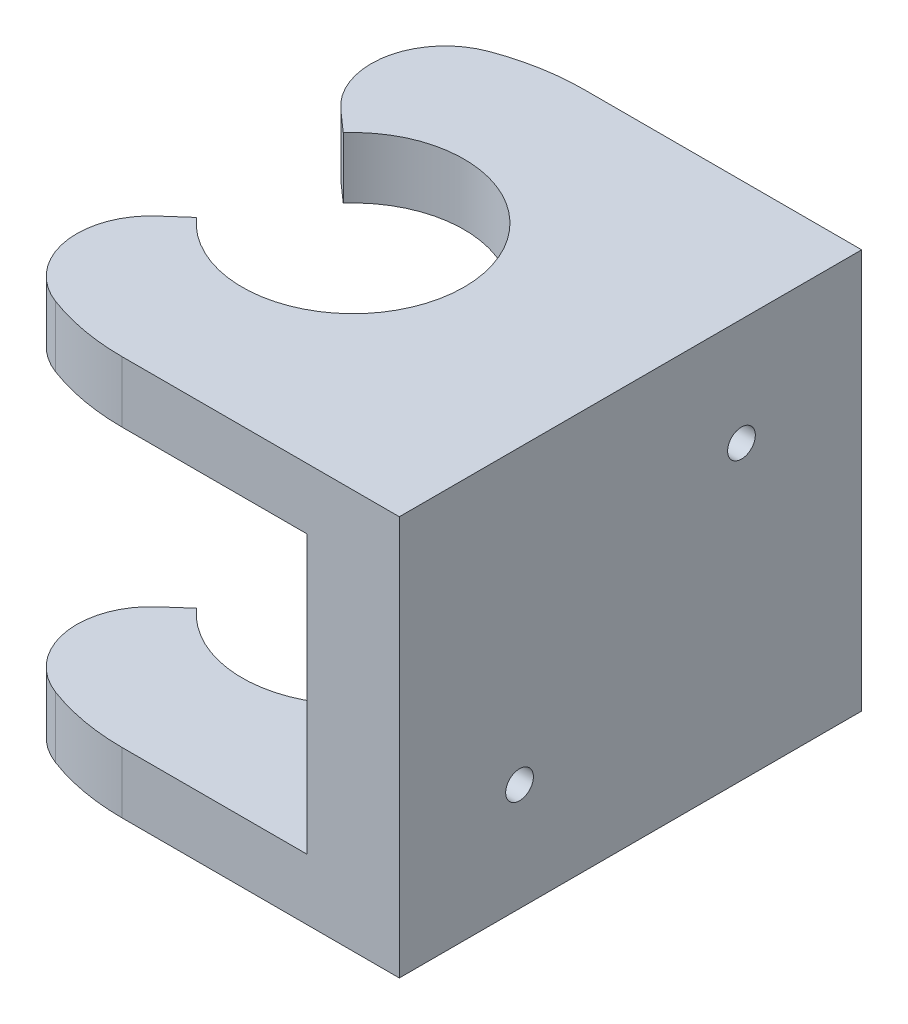
SolidWorks part; units mm, degrees
ref_plane "Front Plane" through (0, 0, 0) normal (0, 0, 1) x (1, 0, 0)
ref_plane "Top Plane" through (0, 0, 0) normal (0, 1, 0) x (1, 0, 0)
ref_plane "Right Plane" through (0, 0, 0) normal (1, 0, 0) x (0, 0, -1)
sketch "Sketch2" plane through (0, 0, 0) normal (0, 1, 0) x (1, 0, 0)
  line L0 (0, 0) -> (15, 0) construction
  line L1 (15, -12.5) -> (0, -12.5) construction
  line L2 (15, -12.5) -> (15, 12.5)
  line L3 (15, 12.5) -> (0, 12.5) construction
  line L5 (-9.375, 8.268) -> (-4.5, 3.9686)
  line L6 (-9.375, -8.268) -> (-4.5, -3.9686)
  line L8 (-4.5, 3.9686) -> (-4.5, -3.9686) construction
  line L9 (-4.5, 0) -> (0, 0) construction
  line L10 (0, 12.5) -> (15, 12.5)
  line L11 (15, -12.5) -> (0, -12.5)
  arc A0 (-4.5, -3.9686) -> (-4.5, 3.9686) centre (0, 0) ccw
  arc A1 (-9.375, -8.268) -> (0, -12.5) centre (0, 0) ccw
  arc A2 (0, 12.5) -> (-9.375, 8.268) centre (0, 0) ccw
  arc A3 (-9.375, -8.268) -> (-9.375, 8.268) centre (0, 0) ccw construction
  point P6 (-0.2805, 12.4969)
  point P7 (-0.2805, -12.5)
  point P16 (-11.8038, 12.5)
  dimension "D1" = 4.5
  dimension "D6" = 6.5
  dimension "D2" = 25
  dimension "D3" = 15
  dimension "D4" = 15
extrude "Boss-Extrude1" add sketch "Sketch2" along normal blind 3.3
sketch "Sketch3" plane through (0, 3.3, 0) normal (0, 1, 0) x (1, 0, 0)
  line L1 (15, 12.5) -> (10, 12.5)
  line L2 (15, 12.5) -> (15, -12.5)
  line L3 (15, -12.5) -> (10, -12.5)
  line L4 (10, 12.5) -> (10, -12.5)
  point P5 (0, 0)
  point P6 (0, 0)
  point P7 (0, 0)
  point P8 (15, 12.5)
  point P10 (15, -12.5)
  dimension "D1" = 5
extrude "Boss-Extrude3" add sketch "Sketch3" along normal blind 15
sketch "Sketch4" plane through (0, 18.3, 0) normal (0, 1, 0) x (1, 0, 0)
  line L0 (15, -12.5) -> (15, 12.5) construction
  line L11 (15, 12.5) -> (10, 12.5) construction
  line L15 (10, -12.5) -> (15, -12.5) construction
  line L23 (10, 12.5) -> (0, 12.5) construction
  line L24 (-9.375, 8.268) -> (-4.5, 3.9686) construction
  line L25 (-4.5, -3.9686) -> (-9.375, -8.268) construction
  line L26 (0, -12.5) -> (10, -12.5) construction
  line L27 (15, -12.5) -> (15, 12.5)
  line L28 (15, 12.5) -> (10, 12.5)
  line L30 (10, -12.5) -> (15, -12.5)
  line L32 (10, 12.5) -> (0, 12.5)
  line L33 (-9.375, 8.268) -> (-4.5, 3.9686)
  line L34 (-4.5, -3.9686) -> (-9.375, -8.268)
  line L35 (0, -12.5) -> (10, -12.5)
  arc A2 (0, 12.5) -> (-9.375, 8.268) centre (0, 0) ccw construction
  arc A3 (-4.5, -3.9686) -> (-4.5, 3.9686) centre (0, 0) ccw construction
  arc A4 (-9.375, -8.268) -> (0, -12.5) centre (0, 0) ccw construction
  arc A5 (0, 12.5) -> (-9.375, 8.268) centre (0, 0) ccw
  arc A6 (-4.5, -3.9686) -> (-4.5, 3.9686) centre (0, 0) ccw
  arc A7 (-9.375, -8.268) -> (0, -12.5) centre (0, 0) ccw
  line M1 (15, -12.5) -> (15, 12.5)
  line M2 (15, 12.5) -> (10, 12.5)
  line M3 (10, 12.5) -> (10, -12.5)
  line M4 (10, -12.5) -> (15, -12.5)
extrude "Boss-Extrude4" add sketch "Sketch4" along normal blind 3.3 contours M3 | M4 M1 M2 M3 region at (12.5, 18.3, 0) region at (5, 18.3, 12.1837)
sketch "Sketch5" plane through (15, 0, 0) normal (1, 0, 0) x (0, 0, -1)
  line L0 (0, 0) -> (0, 21.6) construction
  line L1 (-12.5, 0) -> (12.5, 0) construction
  line L2 (-12.5, 21.6) -> (12.5, 21.6) construction
  line L4 (-6, 5.8) -> (6, 5.8) construction
  line L5 (-6, 5.8) -> (-6, 15.8) construction
  line L6 (-6, 15.8) -> (6, 15.8) construction
  line L7 (6, 5.8) -> (6, 15.8) construction
  line L8 (-6, 5.8) -> (6, 15.8) construction
  line L9 (-6, 15.8) -> (6, 5.8) construction
  circle A0 centre (6, 15.8) radius 0.75
  circle A1 centre (-6, 5.8) radius 0.75
  point P6 (0, 10.8)
  dimension "D3" = 1.5
  dimension "D4" = 1.5
  dimension "D1" = 12
  dimension "D2" = 10
extrude "Cut-Extrude1" cut sketch "Sketch5" against normal through all
fillet "Fillet1" radius 4 4 edges at (-9.375, 1.65, 8.268) (-9.375, 1.65, -8.268) (-9.375, 19.95, -8.268) (-9.375, 19.95, 8.268)
